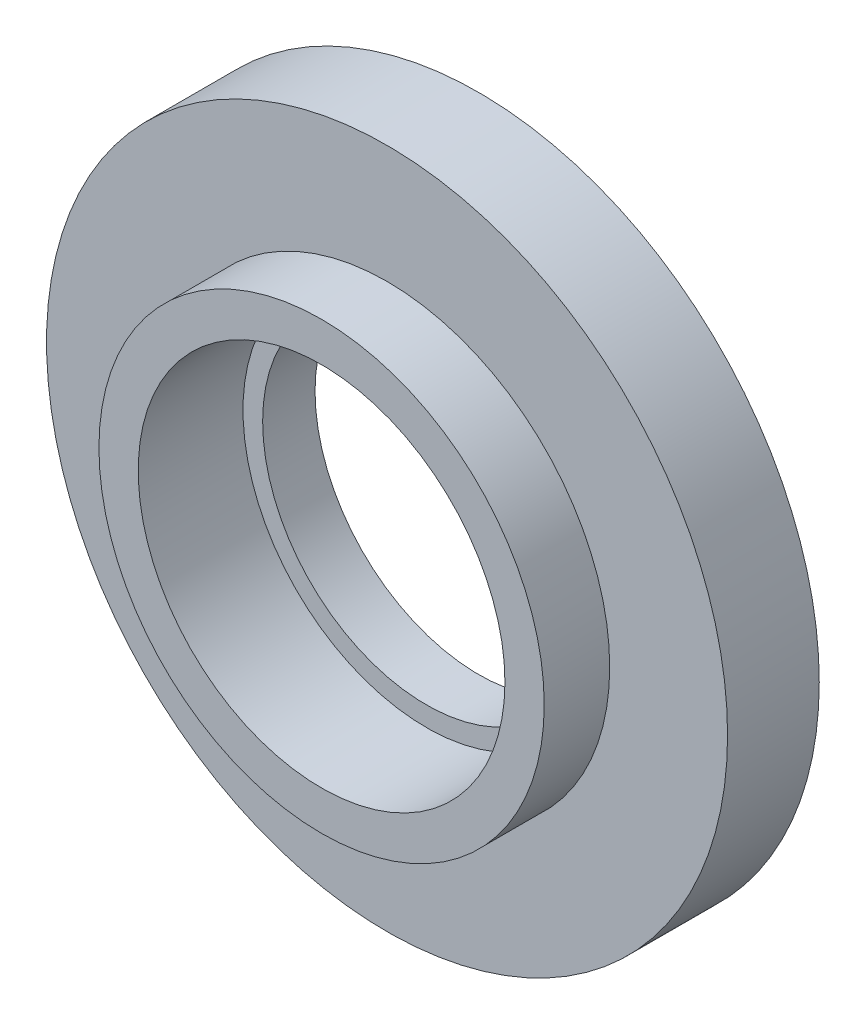
SolidWorks part; units mm, degrees
ref_plane "Front Plane" through (0, 0, 0) normal (0, 0, 1) x (1, 0, 0)
ref_plane "Top Plane" through (0, 0, 0) normal (0, 1, 0) x (1, 0, 0)
ref_plane "Right Plane" through (0, 0, 0) normal (1, 0, 0) x (0, 0, -1)
sketch "Sketch2" plane through (0, 0, 0) normal (0, 1, 0) x (1, 0, 0)
  line L0 (0, 0) -> (-26, 0)
  line L1 (-26, 0) -> (-26, -7)
  line L2 (-26, -7) -> (-17, -7)
  line L3 (-17, -7) -> (-17, -12)
  line L4 (-17, -12) -> (0, -12)
  line L5 (0, -12) -> (0, 0)
  dimension "D1" = 7
  dimension "D2" = 5
  dimension "D3" = 26
  dimension "D4" = 17
revolve "Revolve4" add sketch "Sketch2" angle 360 about L5
sketch "Sketch4" plane through (0, 0, 12) normal (0, 0, 1) x (1, 0, 0)
  circle A0 centre (0, 0) radius 14
  dimension "D1" = 28
extrude "Cut-Extrude1" cut sketch "Sketch4" against normal blind 8
sketch "Sketch5" plane through (0, 0, 0) normal (0, 0, -1) x (-1, 0, 0)
  circle A0 centre (0, 0) radius 12.5
  dimension "D1" = 25
extrude "Cut-Extrude4" cut sketch "Sketch5" against normal blind 8.1
sketch "Sketch7" plane through (0, 0, 0) normal (0, 0, -1) x (-1, 0, 0)
  circle A0 centre (0, 17) radius 2.5
  circle A2 centre (14.7224, 8.5) radius 2.5
  circle A3 centre (14.7224, -8.5) radius 2.5
  circle A4 centre (0, -17) radius 2.5
  circle A5 centre (-14.7224, -8.5) radius 2.5
  circle A6 centre (-14.7224, 8.5) radius 2.5
  point P15 (0, 0)
  dimension "D1" = 6
extrude "Cut-Extrude5" cut sketch "Sketch7" against normal blind 3
